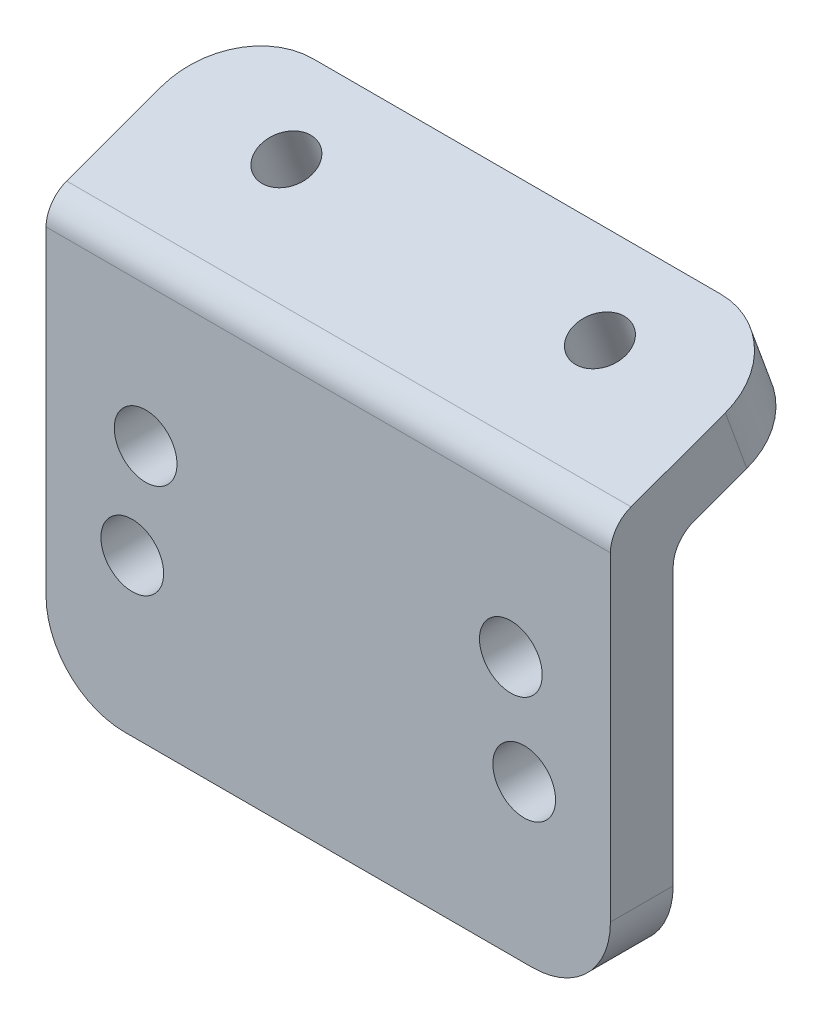
SolidWorks part; units mm, degrees
ref_plane "Plan de face" through (0, 0, 0) normal (0, 0, 1) x (1, 0, 0)
ref_plane "Plan de dessus" through (0, 0, 0) normal (0, 1, 0) x (1, 0, 0)
ref_plane "Plan de droite" through (0, 0, 0) normal (1, 0, 0) x (0, 0, -1)
sketch "Esquisse1" plane through (0, 0, 0) normal (0, 0, 1) x (1, 0, 0)
  line L1 (0, 0) -> (36, 0)
  line L2 (0, 0) -> (0, 24)
  line L3 (0, 24) -> (36, 24)
  line L4 (36, 0) -> (36, 24)
  dimension "D1" = 36
  dimension "D2" = 24
extrude "Boss.-Extru.1" add sketch "Esquisse1" along normal blind 4
sketch "Esquisse2" plane through (0, 0, 4) normal (0, 0, 1) x (1, 0, 0)
  line L0 (18, 0) -> (18, 24) construction
  line L1 (0, 0) -> (36, 0) construction
  line L2 (36, 24) -> (0, 24) construction
  line L3 (5.5, 10) -> (29.6481, 16.4705) construction
  line L4 (5.5, 10) -> (18, 10) construction
  circle A0 centre (5.5, 10) radius 2
  circle A1 centre (30.5, 10) radius 2
  circle A2 centre (29.6481, 16.4705) radius 2
  circle A3 centre (6.3519, 16.4705) radius 2
  dimension "D1" = 25
  dimension "D2" = 10
  dimension "D3" = 4
  dimension "D5" = 25
  dimension "D4" = 15
extrude "Enlèv. mat.-Extru.1" cut sketch "Esquisse2" against normal through all both and the other way through all
sketch "Esquisse3" plane through (36, 0, 0) normal (1, 0, 0) x (0, 0, -1)
  line L0 (0, 24) -> (9.3969, 27.4202)
  line L1 (9.3969, 27.4202) -> (8.0288, 31.179)
  line L2 (8.0288, 31.179) -> (-4, 26.8008)
  line L4 (-4, 26.8008) -> (-4, 24)
  line L5 (0, 0) -> (0, 24) construction
  line L6 (0, 24) -> (-4, 24)
  dimension "D1" = 4
  dimension "D2" = 10
  dimension "D3" = 110
extrude "Boss.-Extru.2" add sketch "Esquisse3" against normal up to vertex (36 mm away) up to point (0, 24, 0)
sketch "Esquisse4" plane through (0, 21.1925, 7.7135) normal (0, -0.9397, -0.342) x (1, 0, 0)
  line L0 (18, -18.2085) -> (18, -15.2024) construction
  line L1 (0, -18.2085) -> (36, -18.2085) construction
  circle A0 centre (8, -13.2085) radius 1.65
  circle A1 centre (28, -13.2085) radius 1.65
  dimension "D2" = 3.3
  dimension "D3" = 5
  dimension "D1" = 10
extrude "Enlèv. mat.-Extru.2" cut sketch "Esquisse4" against normal through all both and the other way through all
fillet "Congé2" radius 5 4 edges at (0, 29.2996, -8.7129) (36, 29.2996, -8.7129) (0, 0, 2) (36, 0, 2)
fillet "Congé3" radius 2 2 edges at (18, 26.8008, 4) (18, 24, 0)
